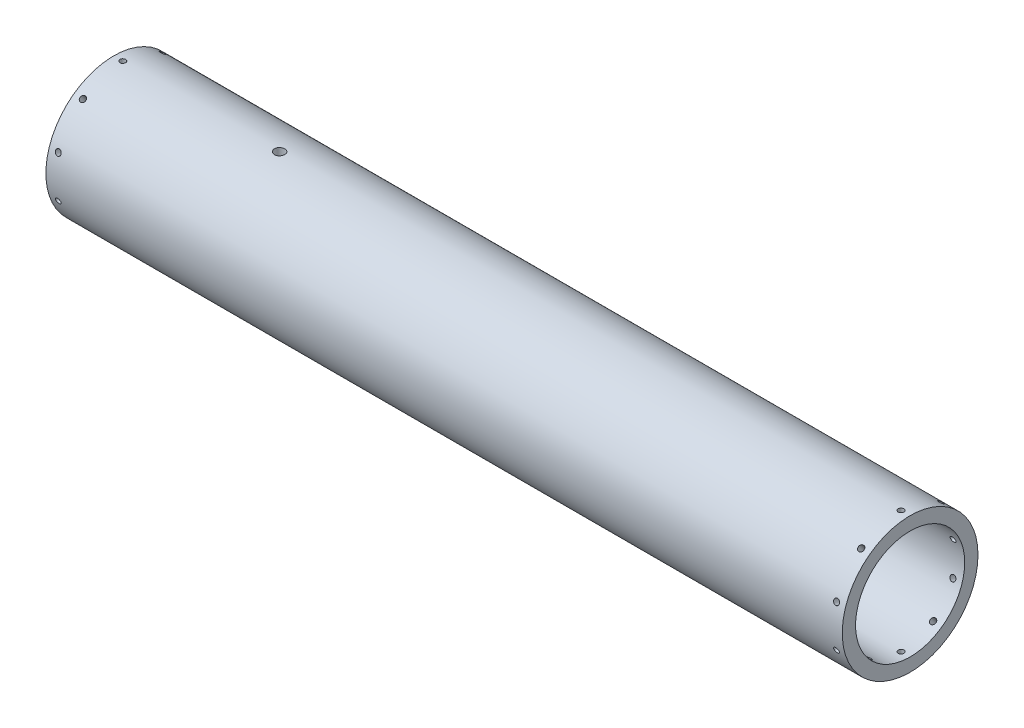
SolidWorks part; units mm, degrees
material "7075-T6 (SN)"
ref_plane "Front Plane" through (0, 0, 0) normal (0, 0, 1) x (1, 0, 0)
ref_plane "Top Plane" through (0, 0, 0) normal (0, 1, 0) x (1, 0, 0)
ref_plane "Right Plane" through (0, 0, 0) normal (1, 0, 0) x (0, 0, -1)
sketch "Sketch1" plane through (0, 0, 0) normal (1, 0, 0) x (0, 0, -1)
  circle A0 centre (0, 0) radius 45.9486
  circle A1 centre (0, 0) radius 57.15
  dimension "D1" = 91.8972
  dimension "D2" = 114.3
extrude "Boss-Extrude1" add sketch "Sketch1" along normal blind 670.56
sketch "Sketch4" plane through (0, 0, 0) normal (0, 0, 1) x (1, 0, 0)
  line L0 (0, 0) -> (0, 88.0135) construction
  line L1 (0, 57.15) -> (0, -57.15) construction
  line L2 (0, -55) -> (0, 55) construction
  line L3 (0, 0) -> (-48.5735, 0) construction
ref_plane "Plane1" through (0, 57.15, 0) normal (0, 1, 0) x (1, 0, 0)
sketch "Sketch6" plane through (0, 57.15, 0) normal (0, 1, 0) x (1, 0, 0)
  line L0 (0, 57.15) -> (0, -57.15) construction
  circle A0 centre (7.62, 0) radius 2.413
  dimension "D1" = 4.826
  dimension "D2" = 7.62
extrude "Cut-Extrude1" cut sketch "Sketch6" against normal blind 15.24
sketch "Sketch7" plane through (0, 57.15, 0) normal (0, 1, 0) x (1, 0, 0)
  line L0 (670.56, -57.15) -> (670.56, 57.15) construction
  circle A0 centre (662.94, 0) radius 2.413
  dimension "D2" = 4.826
  dimension "D1" = 7.62
extrude "Cut-Extrude2" cut sketch "Sketch7" against normal blind 15.24
pattern_circular "CirPattern2" count 10 every 36 about axis through (670.56, 0, 0) along (1, 0, 0) of "Cut-Extrude2"
pattern_circular "CirPattern3" count 10 every 36 about axis through (0, 0, 0) along (-1, 0, 0) of "Cut-Extrude1" reverse direction yes
sketch "Sketch8" plane through (0, 57.15, 0) normal (0, 1, 0) x (1, 0, 0)
  line L0 (0, 57.15) -> (0, -57.15) construction
  circle A0 centre (139.7, 0) radius 4.3053
  dimension "D2" = 8.6106
  dimension "D1" = 139.7
extrude "Cut-Extrude3" cut sketch "Sketch8" against normal through all
